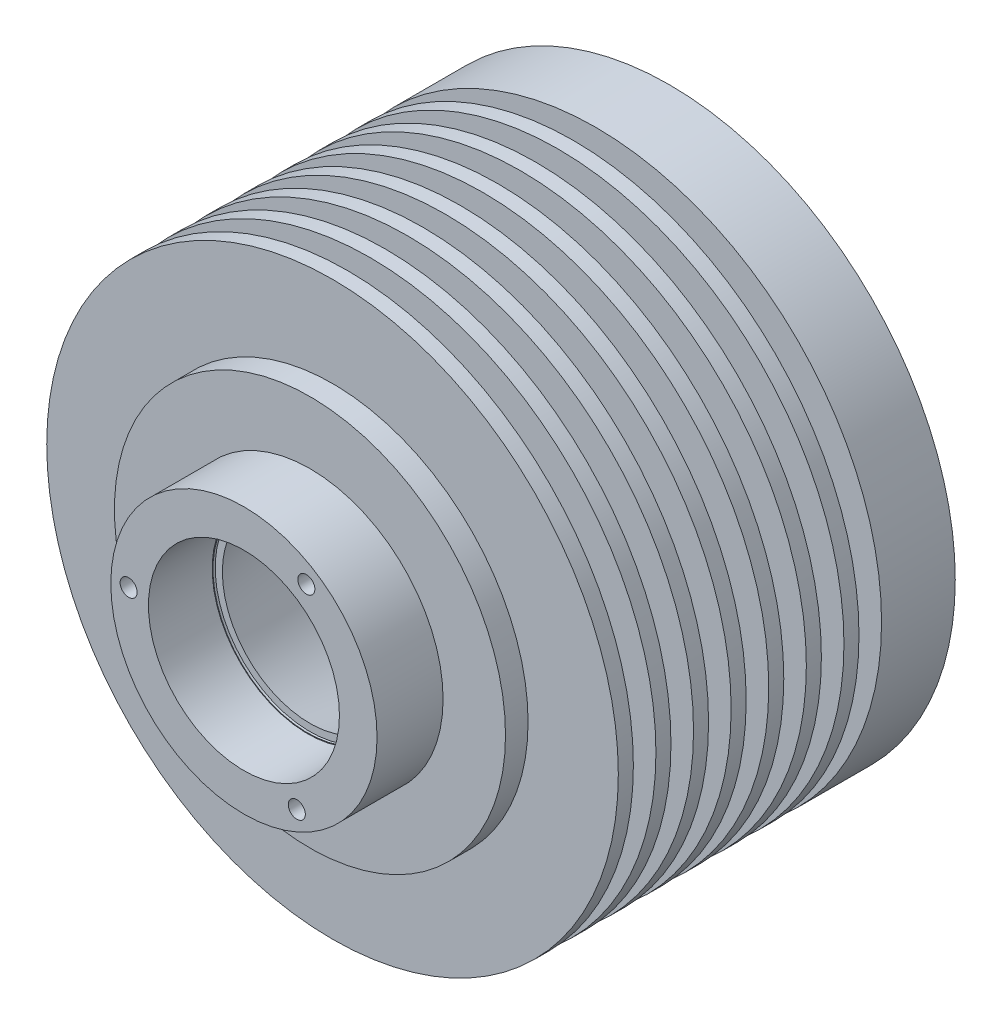
SolidWorks part; units mm, degrees
ref_plane "Plan de face" through (0, 0, 0) normal (0, 0, 1) x (1, 0, 0)
ref_plane "Plan de dessus" through (0, 0, 0) normal (0, 1, 0) x (1, 0, 0)
ref_plane "Plan de droite" through (0, 0, 0) normal (1, 0, 0) x (0, 0, -1)
sketch "Esquisse1" plane through (0, 0, 0) normal (0, 0, 1) x (1, 0, 0)
  circle A0 centre (0, 0) radius 12.7
  circle A1 centre (0, 0) radius 17.7
extrude "Boss.-Extru.1" add sketch "Esquisse1" along normal blind 8.78
sketch "Esquisse2" plane through (0, 0, 0) normal (0, 0, -1) x (-1, 0, 0)
  circle A0 centre (0, 0) radius 11.2
  circle A1 centre (0, 0) radius 38
extrude "Boss.-Extru.2" add sketch "Esquisse2" along normal blind 47.8
chamfer "Chanfrein3" distance 49.8 angle 12.675 1 edges at (-11.2, 0, -47.8)
sketch "Esquisse3" [suppressed] plane through (0, 0, 7.7) normal (0, 0, 1) x (1, 0, 0)
  line L0 (-12.7, 0) -> (-17.7, 0)
  line L1 (12.7, 0) -> (17.7, 0)
  circle A0 centre (0, 0) radius 12.7 construction
  circle A1 centre (0, 0) radius 17.7 construction
  circle A2 centre (0, 0) radius 12.7 construction
other "PerçageAvancé1" [suppressed] parameters "D0"=0
sketch "Esquisse4" plane through (0, 0, 7.7) normal (0, 0, 1) x (1, 0, 0)
  line L0 (-12.7, 0) -> (-17.7, 0) construction
  line L1 (12.7, 0) -> (17.7, 0) construction
  point P0 (-15.2, 0)
  point P4 (15.2, 0)
sketch "Esquisse5" plane through (-15.2, 0, 7.7) normal (0, 1, 0) x (1, 0, 0)
  line L0 (0, 0) -> (0, 1.1176)
  line L1 (0, -0.5588) -> (0, 1.6764) construction
  line L2 (1.7856, 0) -> (1.7856, 1.1176)
  line L3 (0, 0) -> (1.7856, 0)
  line L4 (1.7856, 1.1176) -> (0, 1.1176)
  dimension "D1" = 1.1176
  dimension "D2" = 3.5712
sketch "Sketch1" plane through (0, 0, 8.78) normal (0, 0, 1) x (1, 0, 0)
  line L0 (-12.7, 0) -> (-17.7, 0)
  line L1 (-17.7, 0) -> (12.7, 0)
  line L2 (12.7, 0) -> (17.7, 0)
  circle A0 centre (0, 0) radius 12.7 construction
  circle A1 centre (0, 0) radius 12.7 construction
  circle A2 centre (0, 0) radius 17.7 construction
sketch "Sketch7" plane through (0, 0, 0) normal (0, 0, 1) x (1, 0, 0)
  circle A0 centre (0, 0) radius 26
  circle A1 centre (0, 0) radius 38
extrude "Cut-Extrude2" cut sketch "Sketch7" against normal blind 3
sketch "Sketch12" plane through (0, 0, -47.8) normal (0, 0, -1) x (-1, 0, 0)
  line L0 (38, 0) -> (34, 0)
  circle A0 centre (0, 0) radius 38 construction
sketch "Sketch16" plane through (0, 0, -47.8) normal (0, 0, -1) x (-1, 0, 0)
  line L0 (-13.7438, 35.4275) -> (-13.7438, -26.6666)
  circle A0 centre (0, 0) radius 38 construction
hole_wizard "#4-40 Tapped Hole1" positions "Sketch17" profile "Sketch19" tap size "#4-40" standard "ANSI Inch"
sketch "Sketch17" plane through (0, 0, -47.8) normal (0, 0, -1) x (-1, 0, 0)
  point P0 (-13.7438, -26.6666)
sketch "Sketch19" plane through (13.7438, -26.6666, -47.8) normal (1, 0, 0) x (0, 1, 0)
  line L0 (0, 0) -> (0, 5.6792)
  line L1 (0, 5.6792) -> (1.1303, 5)
  line L2 (1.1303, 5) -> (1.1303, 0)
  line L5 (1.1303, 0) -> (0, 0)
  line L10 (0, 5.6792) -> (-1.1303, 5) construction
  line L11 (0, -6.35) -> (0, 107.95) construction
  dimension "Tap Drill Dia." = 2.2606
  dimension "Tap Drill Depth" = 5
  dimension "Drill Angle" = 118
pattern_circular "CirPattern1" count 4 over 360 about axis through (0, 0, 0) along (0, 0, 1) of "#4-40 Tapped Hole1"
sketch "Sketch20" plane through (0, 0, 8.78) normal (0, 0, 1) x (1, 0, 0)
  line L0 (7.0323, 16.2431) -> (7.0323, -13.6444)
  circle A0 centre (0, 0) radius 17.7 construction
hole_wizard "#4-40 Tapped Hole2" positions "Sketch21" profile "Sketch22" tap size "#4-40" standard "ANSI Inch"
sketch "Sketch21" plane through (0, 0, 8.78) normal (0, 0, 1) x (1, 0, 0)
  point P0 (7.0323, -13.6444)
sketch "Sketch22" plane through (7.0323, -13.6444, 8.78) normal (1, 0, 0) x (0, -1, 0)
  line L0 (0, 0) -> (0, 5.6792)
  line L1 (0, 5.6792) -> (1.1303, 5)
  line L2 (1.1303, 5) -> (1.1303, 0)
  line L5 (1.1303, 0) -> (0, 0)
  line L10 (0, 5.6792) -> (-1.1303, 5) construction
  line L11 (0, -6.35) -> (0, 107.95) construction
  dimension "Tap Drill Dia." = 2.2606
  dimension "Tap Drill Depth" = 5
  dimension "Drill Angle" = 118
pattern_circular "CirPattern2" count 3 over 360 about axis through (0, 0, 0) along (0, 0, 1) of "#4-40 Tapped Hole2"
sketch "Sketch23" plane through (0, 0, 0) normal (0, 0, 1) x (1, 0, 0)
  circle A0 centre (0, 0) radius 12.6
  circle A1 centre (0, 0) radius 13.7
extrude "Boss-Extrude1" add sketch "Sketch23" along normal blind 0.3
pattern_linear "LPattern1" count 8 spacing 5 along (0, 0, -1) of "Cut-Extrude2"
